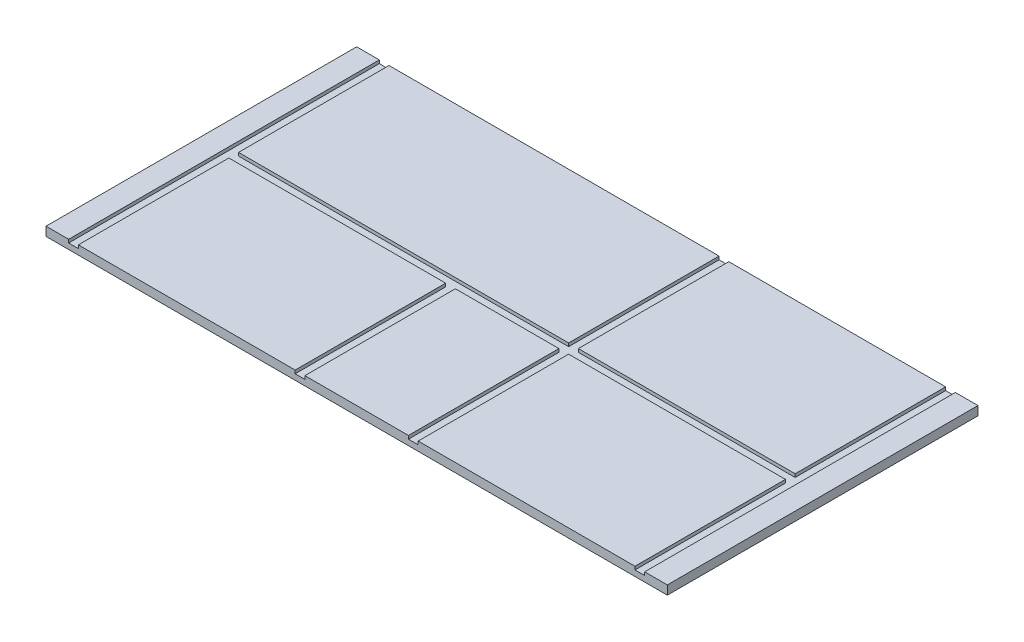
SolidWorks part; units mm, degrees
material "Cedar"
ref_plane "Front Plane" through (0, 0, 0) normal (0, 0, 1) x (1, 0, 0)
ref_plane "Top Plane" through (0, 0, 0) normal (0, 1, 0) x (1, 0, 0)
ref_plane "Right Plane" through (0, 0, 0) normal (1, 0, 0) x (0, 0, -1)
sketch "Sketch1" plane through (0, 0, 0) normal (0, 1, 0) x (1, 0, 0)
  line L1 (-609.6, -304.8) -> (609.6, -304.8)
  line L2 (-609.6, -304.8) -> (-609.6, 304.8)
  line L3 (-609.6, 304.8) -> (609.6, 304.8)
  line L4 (609.6, -304.8) -> (609.6, 304.8)
  line L5 (-609.6, -304.8) -> (609.6, 304.8) construction
  line L6 (-609.6, 304.8) -> (609.6, -304.8) construction
  point P0 (0, 0)
  dimension "D1" = 1219.2
  dimension "D2" = 609.6
extrude "Boss-Extrude1" add sketch "Sketch1" along normal blind 17.4752
sketch "Sketch2" plane through (0, 17.4752, 0) normal (0, 1, 0) x (1, 0, 0)
  line L0 (609.6, 304.8) -> (-609.6, 304.8) construction
  line L1 (-565.15, 304.8) -> (-546.1, 304.8)
  line L2 (-565.15, 304.8) -> (-565.15, -304.8)
  line L3 (-565.15, -304.8) -> (-546.1, -304.8)
  line L4 (-546.1, 304.8) -> (-546.1, 9.525)
  line L5 (-609.6, -304.8) -> (609.6, -304.8) construction
  line L7 (-546.1, 9.525) -> (101.6, 9.525)
  line L8 (-546.1, 9.525) -> (-546.1, -9.525) construction
  line L9 (-546.1, -9.525) -> (-120.65, -9.525)
  line L12 (565.15, 304.8) -> (546.1, 304.8)
  line L13 (565.15, 304.8) -> (565.15, -304.8)
  line L14 (565.15, -304.8) -> (546.1, -304.8)
  line L15 (546.1, 304.8) -> (546.1, 9.525)
  line L17 (-120.65, -9.525) -> (-101.6, -9.525) construction
  line L18 (-120.65, -9.525) -> (-120.65, -304.8)
  line L19 (-120.65, -304.8) -> (-101.6, -304.8)
  line L20 (-101.6, -9.525) -> (-101.6, -304.8)
  line L21 (-546.1, -9.525) -> (-546.1, -304.8)
  line L23 (101.6, -9.525) -> (101.6, -304.8)
  line L24 (101.6, -304.8) -> (120.65, -304.8)
  line L25 (120.65, -9.525) -> (120.65, -304.8)
  line L26 (-101.6, -9.525) -> (101.6, -9.525)
  line L27 (0, 0) -> (0, -9.525) construction
  line L28 (546.1, -9.525) -> (546.1, -304.8)
  line L29 (120.65, -9.525) -> (546.1, -9.525)
  line L30 (-565.15, 304.8) -> (-609.6, 304.8) construction
  line L31 (565.15, 304.8) -> (609.6, 304.8) construction
  line L32 (-609.6, 304.8) -> (-609.6, -304.8) construction
  line L33 (120.65, 9.525) -> (546.1, 9.525)
  line L35 (101.6, 9.525) -> (101.6, 304.8)
  line L36 (101.6, 304.8) -> (120.65, 304.8)
  line L37 (120.65, 9.525) -> (120.65, 304.8)
  line L38 (-546.1, 0) -> (-609.6, 0) construction
  dimension "D1" = 19.05
  dimension "D3" = 425.45
  dimension "D4" = 203.2
  dimension "D5" = 44.45
extrude "Cut-Extrude1" cut sketch "Sketch2" against normal blind 6.35
sketch "Sketch4" plane through (0, 11.1252, 0) normal (0, 1, 0) x (1, 0, 0)
  line L0 (-546.1, -9.525) -> (-546.1, 9.525)
  line L1 (-120.65, -9.525) -> (-101.6, -9.525)
  line L2 (101.6, -9.525) -> (120.65, -9.525)
  line L3 (101.6, 9.525) -> (120.65, 9.525)
  line L4 (120.65, 9.525) -> (120.65, 304.8) construction
  line L5 (120.65, 9.525) -> (120.65, 304.8) construction
  line L6 (-565.15, 304.8) -> (-546.1, 304.8)
  line L7 (565.15, 304.8) -> (546.1, 304.8)
  line L8 (-101.6, -304.8) -> (-120.65, -304.8)
  line L9 (120.65, -304.8) -> (101.6, -304.8)
  line L10 (120.65, 304.8) -> (101.6, 304.8)
  line L11 (120.65, 304.8) -> (101.6, 304.8) construction
  point P27 (555.625, 304.8)
  point P28 (111.125, 9.525)
  point P29 (111.125, -9.525)
  point P30 (-111.125, -9.525)
  point P31 (-546.1, 0)
  point P32 (-555.625, 304.8)
  point P37 (-111.125, -304.8)
  point P42 (111.125, -304.8)
  point P48 (111.125, 304.8)
sketch "Sketch5" plane through (0, 11.1252, 0) normal (0, 1, 0) x (1, 0, 0)
  line L0 (-101.6, -9.525) -> (101.6, -9.525) construction
  point P0 (0, -9.525)
